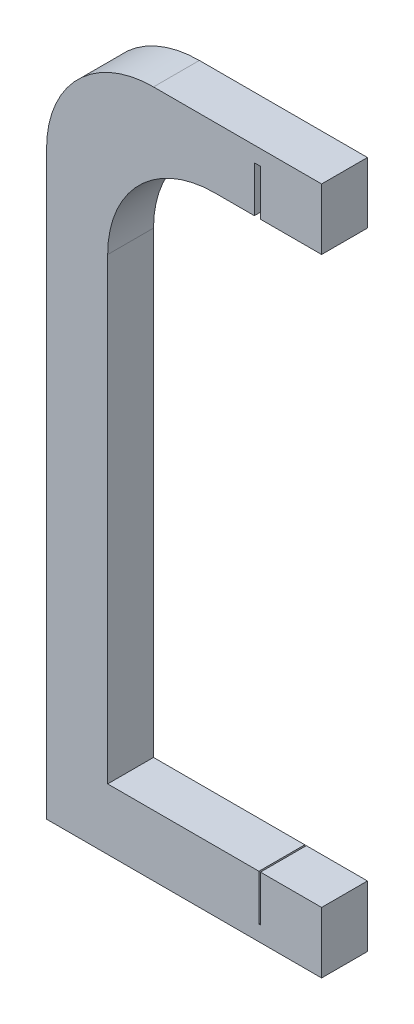
SolidWorks part; units mm, degrees
ref_plane "Front Plane" through (0, 0, 0) normal (0, 0, 1) x (1, 0, 0)
ref_plane "Top Plane" through (0, 0, 0) normal (0, 1, 0) x (1, 0, 0)
ref_plane "Right Plane" through (0, 0, 0) normal (1, 0, 0) x (0, 0, -1)
sketch "Sketch1" plane through (0, 0, 0) normal (0, 0, 1) x (1, 0, 0)
  line L0 (0, 38) -> (0, 0)
  line L1 (0, 0) -> (18, 0)
  line L2 (18, 0) -> (18, 4)
  line L3 (18, 4) -> (4, 4)
  line L4 (4, 4) -> (4, 34)
  line L5 (11, 41) -> (18, 41)
  line L6 (18, 41) -> (18, 45)
  line L7 (18, 45) -> (7, 45)
  arc A0 (7, 45) -> (0, 38) centre (7, 38) ccw
  arc A1 (11, 41) -> (4, 34) centre (11, 34) ccw
  point P11 (0, 45)
  dimension "D6" = 7
  dimension "D7" = 7
  dimension "D3" = 4
  dimension "D4" = 14
  dimension "D5" = 4
extrude "Boss-Extrude1" add sketch "Sketch1" along normal blind 3
sketch "Sketch3" plane through (0, 4, 0) normal (0, 1, 0) x (1, 0, 0)
  line L0 (0, -1.5) -> (13.95, -1.5) construction
  line L1 (0, -3) -> (0, 0) construction
  line L2 (18, 0) -> (4, 0) construction
  line L3 (13.9, -3) -> (14, -3)
  line L4 (13.9, -3) -> (13.9, 0)
  line L5 (13.9, 0) -> (14, 0)
  line L6 (14, -3) -> (14, 0)
  line L7 (13.9, -3) -> (14, 0) construction
  line L8 (13.9, 0) -> (14, -3) construction
extrude "Cut-Extrude1" cut sketch "Sketch3" against normal blind 3
sketch "Sketch4" plane through (0, 41, 0) normal (0, -1, 0) x (1, 0, 0)
  line L0 (0, 1.5) -> (13.8, 1.5) construction
  line L1 (0, 3) -> (0, 0) construction
  line L2 (11, 3) -> (18, 3) construction
  line L3 (13.6, 0) -> (14, 0)
  line L4 (13.6, 0) -> (13.6, 3)
  line L5 (13.6, 3) -> (14, 3)
  line L6 (14, 0) -> (14, 3)
  line L7 (13.6, 0) -> (14, 3) construction
  line L8 (13.6, 3) -> (14, 0) construction
extrude "Cut-Extrude2" cut sketch "Sketch4" against normal blind 3
equation "\"A.L\"= 0.06m"
equation "\"A.h\"= 0.005m"
equation "\"A.d\"= 0.003m"
equation "\"A.delta\"= 45.0001"
equation "\"A.w\"= 0.02m"
equation "\"A.v\"= 0.03m"
equation "\"A.s\"= 0.0075m"
equation "\"A.t\"= 0.005m"
equation "\"B.L\"= 0.04m"
equation "\"B.h\"= 0.004m"
equation "\"B.s\"= 0.008m"
equation "\"B.t\"= 0.004m"
equation "\"C.h\"= 0.0062m"
equation "\"C.d\"= 0.003m"
equation "\"C.L\"= 0.05m"
equation "\"C.wmax\"= 0.005m"
equation "\"D.L\"= 0.045m"
equation "\"D.h\"= 0.004m"
equation "\"D.s\"= 0.01m"
equation "\"D.t\"= 0.004m"
equation "\"a_h\"= 0.0001m"
equation "\"a_d\"= 0.003m"
equation "\"a_L\"= 0.01m"
equation "\"b_h\"= 0.0004m"
equation "\"b_d\"= 0.003m"
equation "\"b_L\"= 0.01m"
equation "\"c_h\"= 0.0001m"
equation "\"c_d\"= 0.003m"
equation "\"c_L\"= 0.01m"
equation "\"d_h\"= 0.0001m"
equation "\"d_d\"= 0.003m"
equation "\"d_L\"= 0.01m"
equation "\"S.h\"= 0.015m"
equation "\"S.L\"= 0.0559m"
equation "\"D1@Sketch1\"=\"D.L\""
equation "\"D2@Sketch1\"=\"D.h\""
equation "\"D3@Sketch1\"=\"D.h\""
equation "\"D4@Sketch1\"=\"D.s\"+0.004"
equation "\"D5@Sketch1\"=\"D.h\""
equation "\"D1@Boss-Extrude1\"=\"A.d\""
equation "\"D1@Sketch3\"=\"D.h\"+\"D.s\"-\"a_h\"/2"
equation "\"D2@Sketch3\"=\"a_h\""
equation "\"D1@Sketch4\"=\"D.h\"+\"D.s\"-\"b_h\"/2"
equation "\"D2@Sketch4\"=\"b_h\""
